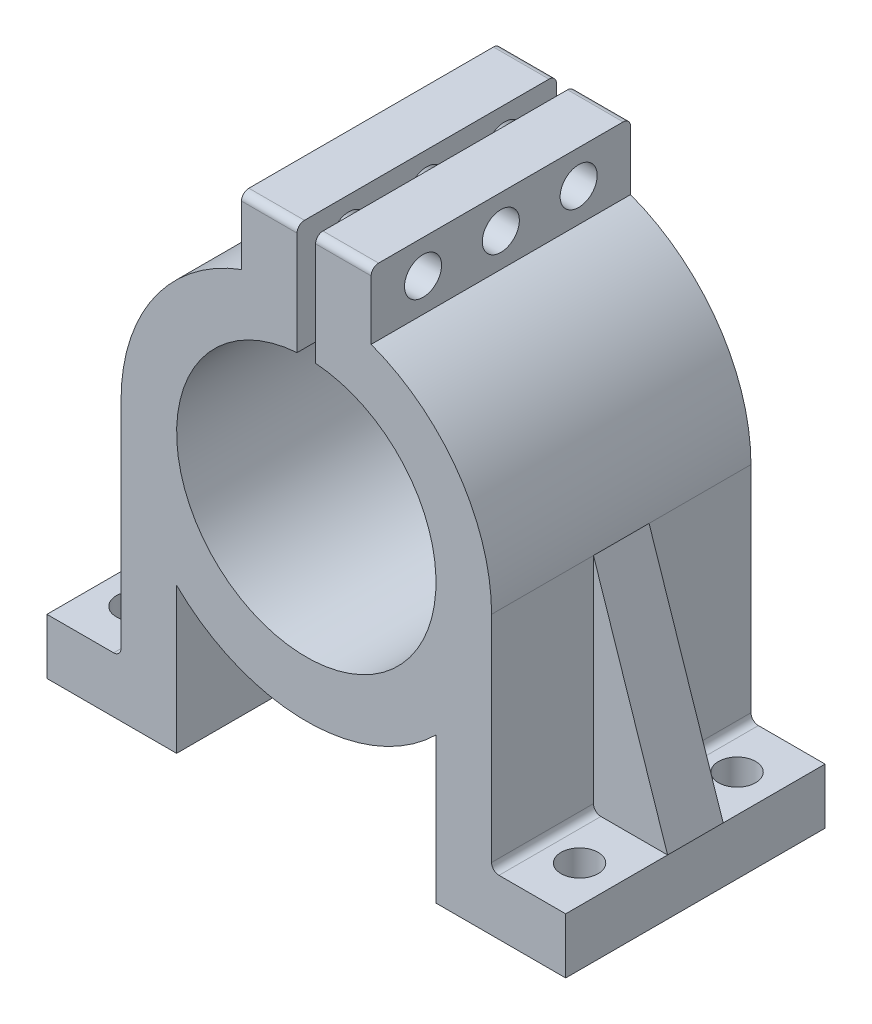
SolidWorks part; units mm, degrees
ref_plane "Alzado" through (0, 0, 0) normal (0, 0, 1) x (1, 0, 0)
ref_plane "Planta" through (0, 0, 0) normal (0, 1, 0) x (1, 0, 0)
ref_plane "Vista lateral" through (0, 0, 0) normal (1, 0, 0) x (0, 0, -1)
sketch "Croquis1" plane through (0, 0, 0) normal (0, 0, 1) x (1, 0, 0)
  line L0 (0.5, 6.9821) -> (0.5, 12.9675)
  line L1 (0, -14.5503) -> (0, -7) construction
  line L2 (0.5, 12.9675) -> (3.5, 12.9675)
  line L3 (3.5, 12.9675) -> (3.5, 9.3675)
  line L4 (-3.5, 12.9675) -> (-3.5, 9.3675)
  line L5 (-0.5, 6.9821) -> (-0.5, 12.9675)
  line L6 (-0.5, 12.9675) -> (-3.5, 12.9675)
  line L7 (-7, -15) -> (-7, -7.1414)
  line L8 (-10, 0) -> (-10, -11.6)
  line L9 (-10.4, -12) -> (-14, -12)
  line L10 (-14, -12) -> (-14, -15)
  line L11 (-14, -15) -> (-7, -15)
  line L12 (10, 0) -> (10, -11.6)
  line L13 (10.4, -12) -> (14, -12)
  line L14 (14, -12) -> (14, -15)
  line L15 (14, -15) -> (7, -15)
  line L16 (7, -15) -> (7, -7.1414)
  arc A0 (-0.5, 6.9821) -> (0.5, 6.9821) centre (0, 0) ccw
  arc A1 (-3.5, 9.3675) -> (-10, 0) centre (0, 0) ccw
  arc A2 (-7, -7.1414) -> (7, -7.1414) centre (0, 0) ccw
  arc A3 (10, 0) -> (3.5, 9.3675) centre (0, 0) ccw
  arc A4 (-10.4, -12) -> (-10, -11.6) centre (-10.4, -11.6) ccw
  arc A5 (10, -11.6) -> (10.4, -12) centre (10.4, -11.6) ccw
  point P7 (-10, -12)
  point P29 (10, -12)
  dimension "D1" = 14
  dimension "D2" = 20
  dimension "D10" = 0.4
  dimension "D11" = 0.4
  dimension "D3" = 0.5
  dimension "D4" = 3
  dimension "D5" = 3.6
  dimension "D6" = 12
  dimension "D7" = 3
  dimension "D8" = 7
  dimension "D9" = 4
extrude "Saliente-Extruir1" add sketch "Croquis1" along normal blind 14
sketch "Croquis2" plane through (0, 0, 14) normal (0, 0, 1) x (1, 0, 0)
  line L1 (-7, -15) -> (-7.4, -15)
  line L2 (-7, -15) -> (-7, -14.6)
  line L3 (-7, -14.6) -> (-7.4, -14.6)
  line L4 (-7.4, -15) -> (-7.4, -14.6)
  line L5 (7, -15) -> (7.4, -15)
  line L6 (7, -15) -> (7, -14.6)
  line L7 (7, -14.6) -> (7.4, -14.6)
  line L8 (7.4, -15) -> (7.4, -14.6)
  dimension "D1" = 0.4
  dimension "D2" = 0.4
  dimension "D3" = 0.4
  dimension "D4" = 0.4
extrude "Cortar-Extruir1" cut sketch "Croquis2" against normal through all both and the other way through all
sketch "Croquis4" plane through (0, 0, 14) normal (0, 0, 1) x (1, 0, 0)
  line L0 (-14, -12) -> (-10, 0)
  line L1 (-10, 0) -> (-10, -11.6) construction
  line L2 (-10, 0) -> (-10, -12)
  line L3 (-10, -12) -> (-14, -12)
  line L4 (14, -12) -> (10, 0)
  line L5 (10, -11.6) -> (10, 0) construction
  line L6 (10, 0) -> (10, -12)
  line L7 (10, -12) -> (14, -12)
  dimension "D1" = 12
  dimension "D2" = 12
extrude "Saliente-Extruir2" add sketch "Croquis4" against normal through all
sketch "Croquis5" plane through (0, 0, 14) normal (0, 0, 1) x (1, 0, 0)
  line L0 (-14, -12) -> (-10, 0)
  line L1 (-10, 0) -> (-10, -12)
  line L2 (-10, -12) -> (-14, -12)
  line L3 (14, -12) -> (10, 0)
  line L4 (10, 0) -> (10, -12)
  line L5 (10, -12) -> (14, -12)
extrude "Cortar-Extruir2" cut sketch "Croquis5" against normal blind 5.5 and the other way through all
sketch "Croquis6" plane through (0, 0, 0) normal (0, 0, -1) x (-1, 0, 0)
  line L0 (-14, -12) -> (-10, 0)
  line L1 (-10, 0) -> (-10, -12)
  line L2 (-10, -12) -> (-14, -12)
  line L3 (14, -12) -> (10, 0)
  line L4 (10, 0) -> (10, -12)
  line L5 (10, -12) -> (14, -12)
  dimension "D1" = 12
extrude "Cortar-Extruir3" cut sketch "Croquis6" against normal blind 5.5
extrude "Saliente-Extruir3" add sketch "Croquis1<2>" along normal through all
sketch "Croquis1<2>" plane through (0, 0, 0) normal (0, 0, 1) x (1, 0, 0) same geometry as "Croquis1"
sketch "Croquis7" plane through (0, -12, 0) normal (0, 1, 0) x (1, 0, 0)
  line L0 (-10, -8.5) -> (-14, -8.5) construction
  line L2 (-14, -14.0001) -> (-14, -8.5) construction
  line L5 (-14, -5.5) -> (-14, 0) construction
  line L6 (-10.4, 0) -> (-14, 0) construction
  line L7 (14, -5.5) -> (14, 0) construction
  line L8 (14, 0) -> (10.4, 0) construction
  line L9 (10.4, -8.5) -> (14, -8.5) construction
  line L10 (14, -14.0001) -> (14, -8.5) construction
  circle A0 centre (-12, -11.25) radius 1
  circle A1 centre (-12, -2.75) radius 1
  circle A2 centre (12, -2.75) radius 1
  circle A3 centre (12, -11.25) radius 1
  point P10 (-12, -8.5)
  dimension "D1" = 2
  dimension "D2" = 2
  dimension "D3" = 2
  dimension "D4" = 2
  dimension "D5" = 2.75
  dimension "D6" = 2
  dimension "D7" = 2
  dimension "D8" = 2.75
  dimension "D9" = 2
  dimension "D10" = 2.75
  dimension "D11" = 2.75
  dimension "D12" = 2
extrude "Cortar-Extruir4" cut sketch "Croquis7" against normal through all
fillet "Redondeo3" radius 0.4 4 edges at (-2, 12.9675, 0) (2, 12.9675, 0) (2, 12.9675, 14.0001) (-2, 12.9675, 14.0001)
sketch "Croquis9" plane through (-3.5, 0, 0) normal (-1, 0, 0) x (0, 0, 1)
  line L0 (13.6001, 12.9675) -> (0.4, 12.9675) construction
  line L1 (7.0001, 14.1082) -> (7.0001, -16.8002) construction
  line L2 (14.0001, 0) -> (14.0001, -11.6) construction
  line L3 (0, 12.5675) -> (0, 9.3675) construction
  line L4 (14.0001, 12.5675) -> (14.0001, 9.3675) construction
  circle A0 centre (2.8, 11.1675) radius 1
  circle A1 centre (7.0001, 11.1675) radius 1
  circle A2 centre (11.2001, 11.1675) radius 1
  dimension "D1" = 2
  dimension "D2" = 2
  dimension "D3" = 2
  dimension "D4" = 1.8
  dimension "D5" = 1.8
  dimension "D6" = 1.8
  dimension "D7" = 7
  dimension "D8" = 2.8
  dimension "D9" = 2.8
extrude "Cortar-Extruir5" cut sketch "Croquis9" against normal through all
